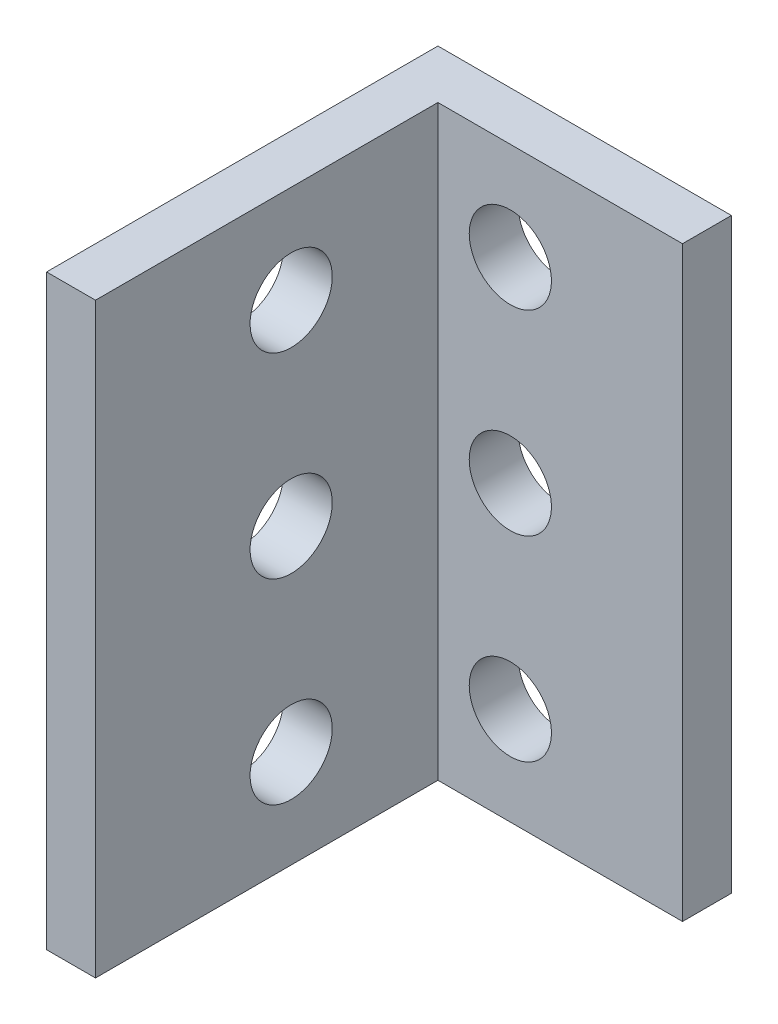
SolidWorks part; units mm, degrees
ref_plane "Front Plane" through (0, 0, 0) normal (0, 0, 1) x (1, 0, 0)
ref_plane "Top Plane" through (0, 0, 0) normal (0, 1, 0) x (1, 0, 0)
ref_plane "Right Plane" through (0, 0, 0) normal (1, 0, 0) x (0, 0, -1)
sketch "Sketch1" plane through (0, 0, 0) normal (0, 0, 1) x (1, 0, 0)
  line L0 (12.7, 19.05) -> (4.826, 19.05) construction
  line L1 (-6.35, 19.05) -> (12.7, 19.05)
  line L2 (-6.35, 19.05) -> (-6.35, -19.05)
  line L3 (-6.35, -19.05) -> (12.7, -19.05)
  line L4 (12.7, 19.05) -> (12.7, -19.05)
  line L7 (4.826, 19.05) -> (4.826, -19.05) construction
  line L8 (4.826, 0) -> (4.826, 12.7) construction
  line L9 (4.826, 0) -> (4.826, -12.7) construction
  line L10 (3.175, 19.05) -> (3.175, -19.05) construction
  line L11 (3.175, 19.05) -> (4.826, 19.05) construction
  circle A6 centre (1.524, -12.7) radius 2.667
  circle A7 centre (1.524, 0) radius 2.667
  circle A8 centre (1.524, 12.7) radius 2.667
  point P0 (0, 0)
  dimension "D3" = 12.7
  dimension "D5" = 12.7
  dimension "D4" = 7.874
  dimension "D1" = 38.1
  dimension "D2" = 19.05
extrude "Boss-Extrude1" add sketch "Sketch1" along normal blind 3.175
sketch "Sketch2" plane through (0, 0, 3.175) normal (0, 0, 1) x (1, 0, 0)
  line L0 (-6.35, -19.05) -> (12.7, -19.05) construction
  line L1 (-6.35, 19.05) -> (-3.175, 19.05)
  line L2 (-6.35, 19.05) -> (-6.35, -19.05)
  line L3 (-6.35, -19.05) -> (-3.175, -19.05)
  line L4 (-3.175, 19.05) -> (-3.175, -19.05)
  dimension "D1" = 3.175
extrude "Boss-Extrude2" add sketch "Sketch2" along normal blind 22.225
sketch "Sketch4" plane through (-3.175, 0, 0) normal (1, 0, 0) x (0, 0, -1)
  line L0 (0, 19.05) -> (-12.7, 19.05) construction
  line L1 (-25.4, 19.05) -> (-3.175, 19.05) construction
  line L2 (-12.7, 19.05) -> (-12.7, -19.05) construction
  line L3 (-25.4, -19.05) -> (-3.175, -19.05) construction
  line L4 (-12.7, 12.7) -> (-12.7, -12.7)
  circle A0 centre (-12.7, 0) radius 2.667
  circle A1 centre (-12.7, 12.7) radius 2.667
  circle A2 centre (-12.7, -12.7) radius 2.667
  point P13 (-12.7, 0)
  dimension "D2" = 5.334
  dimension "D4" = 5.334
  dimension "D5" = 5.334
  dimension "D1" = 12.7
  dimension "D3" = 25.4
extrude "Cut-Extrude1" cut sketch "Sketch4" against normal through all contours A1 | L4 A0 | A2 | L4 A0 region at (-3.175, -10.8675, 10.8675) region at (-3.175, 0, 11.5681) region at (-3.175, 0, 13.8319) region at (-3.175, 14.5325, 14.5325)
